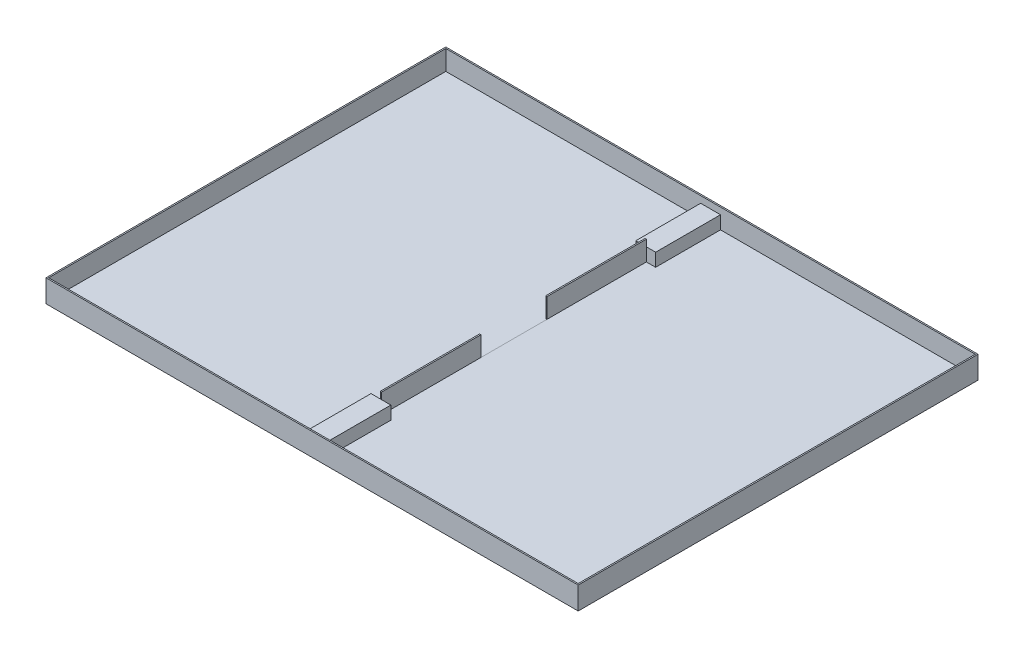
SolidWorks part; units mm, degrees
material "Balsa"
ref_plane "Plano frontal" through (0, 0, 0) normal (0, 0, 1) x (1, 0, 0)
ref_plane "Plano superior" through (0, 0, 0) normal (0, 1, 0) x (1, 0, 0)
ref_plane "Plano direito" through (0, 0, 0) normal (1, 0, 0) x (0, 0, -1)
sketch "Esboço1" plane through (0, 0, 0) normal (0, 0, 1) x (1, 0, 0)
  line L0 (3179.7534, -132.1233) -> (-840.2466, -132.1233)
  line L1 (-840.2466, -132.1233) -> (-840.2466, -152.1233)
  line L4 (-840.2466, -152.1233) -> (3179.7534, -152.1233)
  line L5 (3179.7534, -152.1233) -> (3179.7534, -132.1233)
  dimension "D1" = 4020
  dimension "D3" = 20
extrude "Ressalto-extrusão1" add sketch "Esboço1" along normal blind 3020
sketch "Esboço2" plane through (0, -132.1233, 0) normal (0, 1, 0) x (1, 0, 0)
  line L0 (-830.2466, -10) -> (-830.2466, -3010)
  line L1 (-840.2466, 0) -> (3179.7534, 0)
  line L2 (-840.2466, 0) -> (-840.2466, -3020)
  line L3 (-840.2466, -3020) -> (3179.7534, -3020)
  line L4 (3179.7534, 0) -> (3179.7534, -3020)
  line L5 (-830.2466, -3010) -> (3169.7534, -3010)
  line L6 (3169.7534, -10) -> (3169.7534, -3010)
  line L7 (-830.2466, -10) -> (3169.7534, -10)
  line L8 (1169.7534, -500) -> (1169.7534, -1250) construction
  line L9 (1164.7534, -500) -> (1164.7534, -1250)
  line L10 (1174.7534, -500) -> (1174.7534, -1250)
  line L11 (976.4547, -1500) -> (1352.409, -1500) construction
  line L12 (1164.7534, -1750) -> (1174.7534, -1750)
  line L13 (1164.7534, -1250) -> (1174.7534, -1250)
  line L14 (1164.7534, -2500) -> (1174.7534, -2500)
  line L15 (1164.7534, -1750) -> (1164.7534, -2500)
  line L16 (1164.7534, -10) -> (1164.7534, -2990) construction
  line L17 (1169.7534, -1750) -> (1169.7534, -2500) construction
  line L18 (1169.7534, -10) -> (1169.7534, -2990) construction
  line L19 (1174.7534, -1750) -> (1174.7534, -2500)
  line L20 (1174.7534, -10) -> (1174.7534, -2990) construction
  line L21 (1164.7534, -500) -> (1174.7534, -500)
  line L23 (-830.2466, -10) -> (3169.7534, -10) construction
  line L25 (-830.2466, -3010) -> (3169.7534, -3010) construction
  line L26 (976.4547, -500) -> (1352.409, -500) construction
  line L27 (976.4547, -2500) -> (1352.409, -2500) construction
  point P34 (0, 0)
  point P35 (0, 0)
  point P36 (0, 0)
  point P37 (1169.7534, -10)
  line M9 (3179.7534, 0) -> (-840.2466, 0)
  line M10 (-840.2466, 0) -> (-840.2466, -3020)
  line M11 (-840.2466, -3020) -> (3179.7534, -3020)
  line M12 (3179.7534, -3020) -> (3179.7534, 0)
  dimension "D4" = 500
  dimension "D1" = 10
  dimension "D2" = 5
  dimension "D3" = 5
  dimension "D5" = 1000
  dimension "D6" = 1000
extrude "Ressalto-extrusão2" add sketch "Esboço2" along normal blind 150 contours L19 L12 L15 L14 | L21 L9 L13 L10 | L0 L7 L6 L5 M12 M9 M10 M11 region at (1169.7534, -132.1233, 5.028) region at (1169.7534, -132.1233, 875) region at (1169.7534, -132.1233, 2125)
sketch "Esboço3" plane through (0, -132.1233, 0) normal (0, 1, 0) x (1, 0, 0)
  line L0 (1169.7534, -500) -> (1169.7534, -10) construction
  line L1 (1164.7534, -500) -> (1174.7534, -500) construction
  line L2 (-830.2466, -10) -> (3169.7534, -10) construction
  line L3 (1169.7534, -2500) -> (1169.7534, -3010) construction
  line L4 (1094.7534, -10) -> (1244.7534, -10)
  line L5 (1094.7534, -10) -> (1094.7534, -500)
  line L6 (1094.7534, -500) -> (1244.7534, -500)
  line L7 (1244.7534, -10) -> (1244.7534, -500)
  line L8 (1094.7534, -10) -> (1244.7534, -500) construction
  line L9 (1094.7534, -500) -> (1244.7534, -10) construction
  line L10 (1164.7534, -2500) -> (1174.7534, -2500) construction
  line L11 (-830.2466, -3010) -> (3169.7534, -3010) construction
  line L13 (1094.7534, -2500) -> (1244.7534, -2500)
  line L14 (1094.7534, -2500) -> (1094.7534, -3010)
  line L15 (1094.7534, -3010) -> (1244.7534, -3010)
  line L16 (1244.7534, -2500) -> (1244.7534, -3010)
  line L17 (1094.7534, -2500) -> (1244.7534, -3010) construction
  line L18 (1094.7534, -3010) -> (1244.7534, -2500) construction
  point P6 (1169.7534, -255)
  point P11 (1169.7534, -2755)
  dimension "D1" = 150
extrude "Ressalto-extrusão3" add sketch "Esboço3" along normal blind 100
sketch "Esboço4" plane through (0, -132.1233, 0) normal (0, 1, 0) x (1, 0, 0)
  line L0 (1174.7534, -1750) -> (1174.7534, -2500) construction
  line L1 (3169.7534, -10) -> (1174.7534, -10)
  line L2 (3169.7534, -10) -> (3169.7534, -3010)
  line L3 (3169.7534, -3010) -> (1174.7534, -3010)
  line L4 (1174.7534, -10) -> (1174.7534, -3010)
  line L5 (-830.2466, -3010) -> (1094.7534, -3010) construction
extrude "Ressalto-extrusão4" add sketch "Esboço4" along normal blind 1
